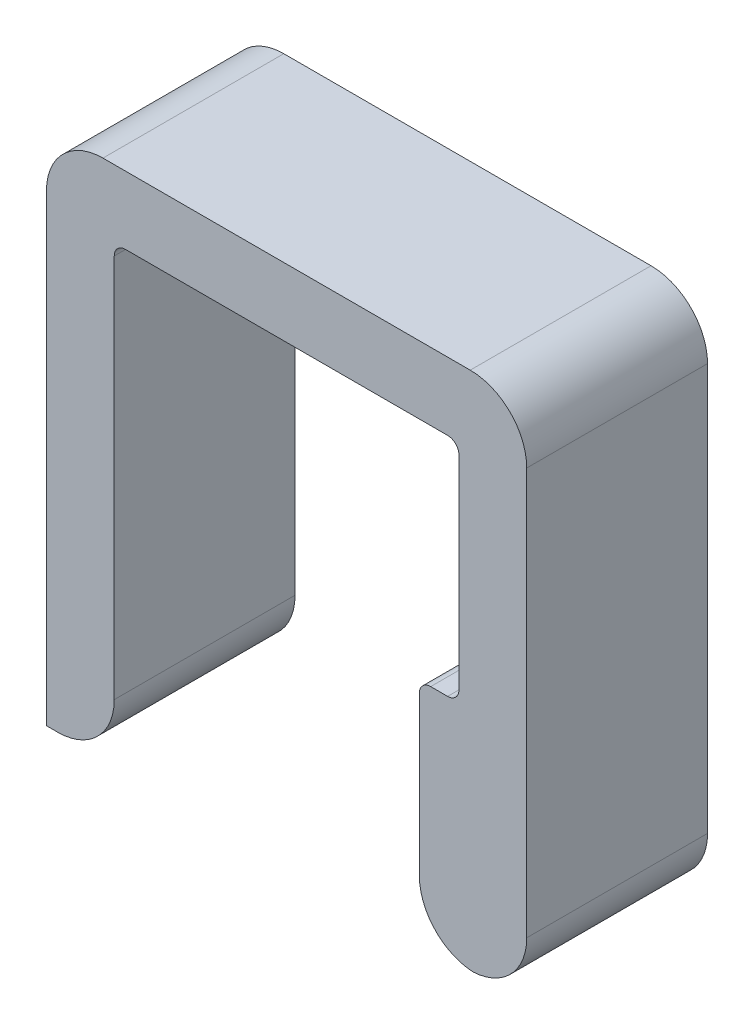
SolidWorks part; units mm, degrees
ref_plane "Front Plane" through (0, 0, 0) normal (0, 0, 1) x (1, 0, 0)
ref_plane "Top Plane" through (0, 0, 0) normal (0, 1, 0) x (1, 0, 0)
ref_plane "Right Plane" through (0, 0, 0) normal (1, 0, 0) x (0, 0, -1)
sketch "Sketch1" plane through (0, 0, 0) normal (0, 0, 1) x (1, 0, 0)
  line L0 (15.25, 0) -> (11.75, 0)
  line L1 (-15.25, 20) -> (15.25, 20) construction
  line L2 (-15.25, 20) -> (-15.25, -20) construction
  line L3 (-15.25, -20) -> (15.25, -20) construction
  line L4 (15.25, 20) -> (15.25, -20) construction
  line L5 (-15.25, 20) -> (15.25, -20) construction
  line L6 (-15.25, -20) -> (15.25, 20) construction
  line L7 (11.75, 0) -> (11.75, -20)
  line L8 (15.25, 0) -> (15.25, 20)
  line L9 (15.25, 20) -> (-15.25, 20)
  line L10 (-15.25, 20) -> (-15.25, -20)
  line L11 (11.75, -20) -> (21.25, -20)
  line L12 (21.25, -20) -> (21.25, 26)
  line L13 (21.25, 26) -> (-21.25, 26)
  line L14 (-21.25, 26) -> (-21.25, -20)
  line L15 (-21.25, -20) -> (-15.25, -20)
  point P0 (0, 0)
  dimension "D1" = 30.5
  dimension "D2" = 40
  dimension "D3" = 3.5
  dimension "D4" = 20
  dimension "D5" = 6
  dimension "D6" = 6
  dimension "D7" = 6
extrude "Boss-Extrude1" add sketch "Sketch1" along normal blind 16
fillet "Fillet1" radius 5 5 edges at (21.25, 26, 8) (-21.25, 26, 8) (11.75, -20, 8) (-15.25, -20, 8) (21.25, -20, 8)
fillet "Fillet2" radius 1 4 edges at (15.25, 0, 8) (11.75, 0, 8) (15.25, 20, 8) (-15.25, 20, 8)
